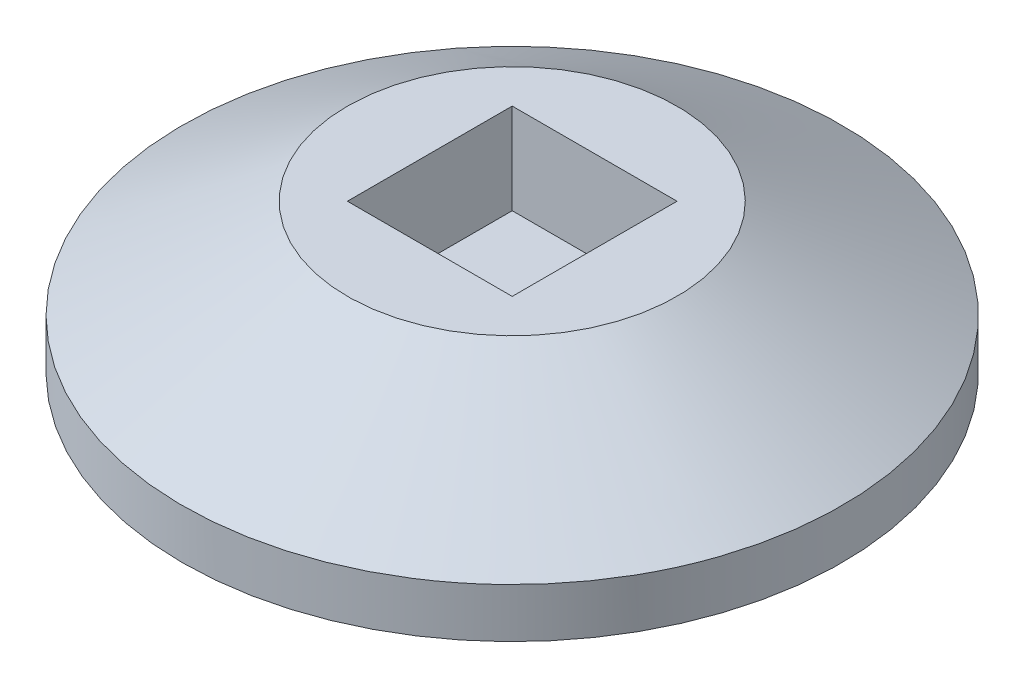
SolidWorks part; units mm, degrees
ref_plane "Front Plane" through (0, 0, 0) normal (0, 0, 1) x (1, 0, 0)
ref_plane "Top Plane" through (0, 0, 0) normal (0, 1, 0) x (1, 0, 0)
ref_plane "Right Plane" through (0, 0, 0) normal (1, 0, 0) x (0, 0, -1)
sketch "Sketch1" plane through (0, 0, 0) normal (0, 1, 0) x (1, 0, 0)
  circle A0 centre (0, 0) radius 20
extrude "Boss-Extrude1" add sketch "Sketch1" along normal mid plane 3 contours A0
ref_plane "Plane1" through (0, 7.5, 0) normal (0, 1, 0) x (1, 0, 0)
sketch "Sketch4" plane through (0, 7.5, 0) normal (0, 1, 0) x (1, 0, 0)
  circle A0 centre (0, 0) radius 10
loft "Loft1" add section "Sketch4" section edge at (0, 1.5, 20) connector at (-6.4273, 7.5, -7.6609) connector at (-15.749, 1.5, -12.3275)
sketch "Sketch5" plane through (0, 7.5, 0) normal (0, 1, 0) x (1, 0, 0)
  line L1 (-5, 5) -> (5, 5)
  line L2 (-5, 5) -> (-5, -5)
  line L3 (-5, -5) -> (5, -5)
  line L4 (5, 5) -> (5, -5)
  line L5 (-5, 5) -> (5, -5) construction
  line L6 (-5, -5) -> (5, 5) construction
  point P0 (0, 0)
extrude "Cut-Extrude1" cut sketch "Sketch5" against normal blind 5.5 contours L2 L3 L4 L1
